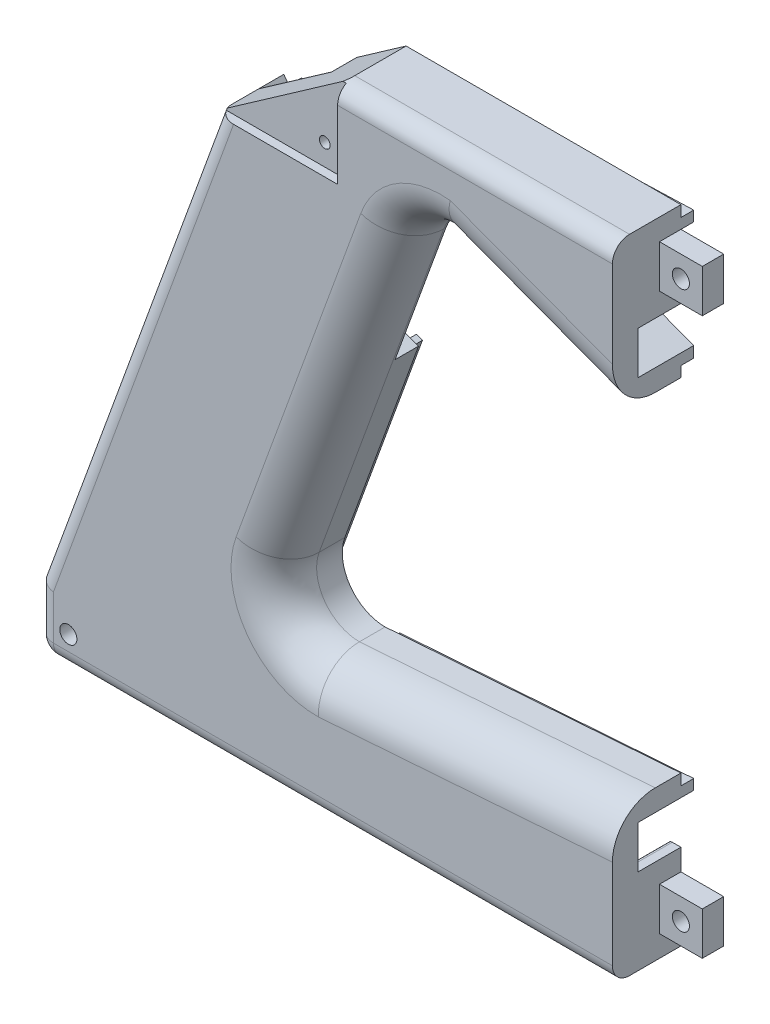
SolidWorks part; units mm, degrees
ref_plane "Ebene vorne" through (0, 0, 0) normal (0, 0, 1) x (1, 0, 0)
ref_plane "Ebene oben" through (0, 0, 0) normal (0, 1, 0) x (1, 0, 0)
ref_plane "Ebene rechts" through (0, 0, 0) normal (1, 0, 0) x (0, 0, -1)
sketch "Skizze1" plane through (0, 0, 0) normal (0, 0, 1) x (1, 0, 0)
  line L0 (-49.3963, -26.5806) -> (-78.5059, -106.5806)
  line L1 (0, -35) -> (-40, -20)
  line L2 (0, 0) -> (0, -35)
  line L3 (0, -115) -> (0, -150)
  line L4 (-69.1078, -120) -> (0, -115)
  line L5 (-134.6051, -135) -> (-134.6051, -150)
  line L6 (0, 0) -> (-64.1971, 0)
  line L7 (-64.1971, 0) -> (-92.76, -20)
  line L8 (-92.76, -20) -> (-134.6051, -135)
  line L9 (-134.6051, -150) -> (0, -150)
  arc A0 (-40, -20) -> (-49.3963, -26.5806) centre (-39.9991, -30) ccw
  arc A1 (-78.5059, -106.5806) -> (-69.1078, -120) centre (-69.1087, -110) ccw
  dimension "D6" = 110
  dimension "D5" = 70
  dimension "D3" = 10
  dimension "D4" = 10
  dimension "D1" = 35
  dimension "D2" = 40
  dimension "D7" = 80
  dimension "D8" = 69.1078
  dimension "D9" = 15
  dimension "D10" = 9.3972
  dimension "D11" = 9.3972
  dimension "D12" = 69.2894
  dimension "D13" = 35
  dimension "D14" = 15
  dimension "D15" = 20
  dimension "D17" = 43
  dimension "D18" = 35
extrude "Aufsatz-Linear austragen1" add sketch "Skizze1" along normal blind 16
sketch "Skizze2" plane through (0, 0, 0) normal (1, 0, 0) x (0, 0, -1)
  line L0 (0, -35) -> (0, 0) construction
  line L1 (0, -5) -> (-5, -5)
  line L2 (0, -5) -> (0, -15)
  line L3 (0, -15) -> (-5, -15)
  line L4 (-5, -5) -> (-5, -15)
  line L5 (-16, 0) -> (0, 0) construction
  dimension "D1" = 5
  dimension "D2" = 10
  dimension "D3" = 5
extrude "Aufsatz-Linear austragen2" add sketch "Skizze2" along normal blind 10
sketch "Skizze3" plane through (0, 0, 5) normal (0, 0, 1) x (1, 0, 0)
  line L0 (10, -15) -> (0, -15) construction
  line L1 (10, -5) -> (10, -15) construction
  circle A0 centre (5, -10) radius 2
  dimension "D2" = 4
  dimension "D1" = 5
  dimension "D3" = 5
extrude "Schnitt-Linear austragen1" cut sketch "Skizze3" against normal through all
sketch "Skizze4" plane through (0, 0, 0) normal (1, 0, 0) x (0, 0, -1)
  line L0 (0, -150) -> (0, -115) construction
  line L1 (0, -135) -> (-5, -135)
  line L2 (0, -135) -> (0, -145)
  line L3 (0, -145) -> (-5, -145)
  line L4 (-5, -135) -> (-5, -145)
  line L5 (-16, -150) -> (0, -150) construction
  dimension "D1" = 5
  dimension "D2" = 10
  dimension "D3" = 5
extrude "Aufsatz-Linear austragen3" add sketch "Skizze4" along normal blind 10
sketch "Skizze5" plane through (0, 0, 5) normal (0, 0, 1) x (1, 0, 0)
  line L0 (10, -135) -> (10, -145) construction
  line L1 (10, -135) -> (0, -135) construction
  circle A0 centre (5, -140) radius 2
  dimension "D1" = 4
  dimension "D2" = 5
  dimension "D3" = 5
extrude "Schnitt-Linear austragen2" cut sketch "Skizze5" against normal through all
sketch "Skizze10" plane through (0, 0, 16) normal (0, 0, 1) x (1, 0, 0)
  line L0 (-92.76, -20) -> (-64.1971, -20)
  line L1 (-64.1971, -20) -> (-64.1971, 0)
  line L2 (-64.1971, 0) -> (-92.76, -20) construction
  line L3 (-64.1971, 0) -> (-92.76, -20)
  dimension "D1" = 20
extrude "Schnitt-Linear austragen3" cut sketch "Skizze10" against normal blind 2
sketch "Skizze11" plane through (0, 0, 14) normal (0, 0, 1) x (1, 0, 0)
  line L0 (-64.1971, -20) -> (-64.1971, 0) construction
  line L1 (-92.76, -20) -> (-64.1971, -20) construction
  circle A0 centre (-69.1971, -15) radius 1.25
  dimension "D1" = 2.5
  dimension "D2" = 5
  dimension "D3" = 5
extrude "Schnitt-Linear austragen4" cut sketch "Skizze11" against normal through all
sketch "Skizze13" plane through (0, 0, 16) normal (0, 0, 1) x (1, 0, 0)
  line L0 (-134.6051, -150) -> (0, -150) construction
  line L1 (-134.6051, -135) -> (-134.6051, -150) construction
  circle A0 centre (-127.1051, -142.5) radius 2
  dimension "D3" = 4
  dimension "D1" = 7.5
  dimension "D2" = 7.5
extrude "Schnitt-Linear austragen5" cut sketch "Skizze13" against normal through all
sketch "Skizze14" plane through (0, 0, 0) normal (0, 0, -1) x (-1, 0, 0)
  line L0 (134.6051, -135) -> (134.6051, -150)
  line L1 (134.6051, -135) -> (134.6051, -150) construction
  line L2 (134.6051, -150) -> (89.6051, -150)
  line L3 (134.6051, -150) -> (0, -150) construction
  line L4 (89.6051, -150) -> (89.6051, -145)
  line L5 (89.6051, -145) -> (59.6051, -145)
  line L6 (59.6051, -145) -> (59.6051, -140)
  line L7 (59.6051, -140) -> (119.6051, -140)
  line L8 (119.6051, -140) -> (119.6051, -135)
  line L9 (119.6051, -135) -> (134.6051, -135)
  dimension "D1" = 15
  dimension "D2" = 45
  dimension "D3" = 60
  dimension "D4" = 5
  dimension "D5" = 5
  dimension "D6" = 15
extrude "Schnitt-Linear austragen6" cut sketch "Skizze14" against normal blind 9
sketch "Skizze15" plane through (0, 0, 0) normal (0, 0, -1) x (-1, 0, 0)
  line L0 (108.9626, -73.3019) -> (131.4126, -135)
  line L1 (134.6051, -135) -> (119.6051, -135) construction
  line L2 (131.4126, -135) -> (119.6051, -135)
  line L3 (119.6051, -135) -> (119.6051, -140)
  line L4 (119.6051, -140) -> (101.6596, -140)
  line L5 (119.6051, -140) -> (59.6051, -140) construction
  line L6 (108.9626, -73.3019) -> (99.5638, -47.4719)
  line L7 (99.5638, -47.4719) -> (64.794, -60.1236)
  line L8 (64.794, -60.1236) -> (93.8587, -140)
  line L9 (93.8587, -140) -> (101.6596, -140)
  line L10 (92.76, -20) -> (134.6051, -135) construction
  line L11 (78.5059, -106.5806) -> (49.3963, -26.5806) construction
  dimension "D1" = 3
  dimension "D2" = 3
  dimension "D3" = 85
extrude "Schnitt-Linear austragen7" cut sketch "Skizze15" against normal blind 9
sketch "Skizze24" plane through (0, 0, 0) normal (0, 0, -1) x (-1, 0, 0)
  line L0 (61.291, -59.2699) -> (49.3963, -26.5806)
  line L1 (78.5059, -106.5806) -> (49.3963, -26.5806) construction
  line L2 (49.3963, -26.5806) -> (40, -20)
  line L3 (40, -20) -> (40, -15.9566)
  line L4 (61.291, -59.2699) -> (64.1102, -58.2441)
  line L5 (64.1102, -58.2441) -> (48.723, -15.9566)
  line L6 (48.723, -15.9566) -> (40, -15.9566)
  line L7 (99.5638, -47.4719) -> (64.794, -60.1236) construction
  dimension "D1" = 3
  dimension "D2" = 45
  dimension "D3" = 2
extrude "Schnitt-Linear austragen17" cut sketch "Skizze24" against normal blind 5.5
sketch "Skizze25" plane through (0, 0, 0) normal (0, 0, -1) x (-1, 0, 0)
  line L0 (64.1102, -58.2441) -> (68.8088, -56.5344)
  line L1 (68.8088, -56.5344) -> (59.2345, -30.2222)
  line L2 (59.2345, -30.2222) -> (54.5359, -31.9319)
  line L3 (64.1102, -58.2441) -> (48.723, -15.9566) construction
  line L4 (54.5359, -31.9319) -> (64.1102, -58.2441)
  dimension "D1" = 5
  dimension "D2" = 28
extrude "Schnitt-Linear austragen18" cut sketch "Skizze25" against normal blind 7.5
sketch "Skizze27" plane through (0, 0, 0) normal (0, 0, -1) x (-1, 0, 0)
  line L0 (59.2345, -30.2222) -> (54.5359, -31.9319)
  line L1 (54.5359, -31.9319) -> (48.723, -15.9566)
  line L2 (48.723, -15.9566) -> (40, -15.9566)
  line L3 (40, -15.9566) -> (40, -20)
  line L4 (40, -20) -> (34.4371, -22.0861)
  line L5 (40, -20) -> (0, -35) construction
  line L6 (34.4371, -22.0861) -> (31.6281, -14.5954)
  line L7 (31.6281, -14.5954) -> (31.6281, -6.5954)
  line L8 (31.6281, -6.5954) -> (59.2345, -7.2222)
  line L9 (59.2345, -7.2222) -> (59.2345, -30.2222)
  dimension "D1" = 8
  dimension "D2" = 8
  dimension "D3" = 27.6064
  dimension "D4" = 23
extrude "Schnitt-Linear austragen19" cut sketch "Skizze27" against normal blind 5.5
sketch "Skizze28" plane through (0, 0, 5.5) normal (0, 0, -1) x (-1, 0, 0)
  line L0 (54.5359, -31.9319) -> (64.1102, -58.2441) construction
  line L2 (59.2345, -30.2222) -> (54.5359, -31.9319) construction
  circle A0 centre (45.5619, -16.0427) radius 1.5
  dimension "D2" = 3
  dimension "D1" = 3
  dimension "D3" = 18
sketch "Skizze29" plane through (0, 0, 0) normal (0, 0, -1) x (-1, 0, 0)
  line L0 (68.8088, -56.5344) -> (83.8443, -51.0634)
  line L1 (83.8443, -51.0634) -> (73.2443, -21.932)
  line L2 (73.2443, -21.932) -> (58.2087, -27.403)
  line L3 (58.2087, -27.403) -> (68.8088, -56.5344)
  dimension "D1" = 16
  dimension "D2" = 31
extrude "Schnitt-Linear austragen20" cut sketch "Skizze29" against normal blind 5
sketch "Skizze30" plane through (0, 0, 5) normal (0, 0, -1) x (-1, 0, 0)
  line L0 (68.8088, -56.5344) -> (83.8443, -51.0634) construction
  line L1 (83.8443, -51.0634) -> (73.2443, -21.932) construction
  circle A0 centre (80.7257, -49.8039) radius 1.25
  dimension "D1" = 2.5
  dimension "D2" = 2.25
  dimension "D3" = 2.5
extrude "Aufsatz-Linear austragen9" add sketch "Skizze30" along normal blind 5
sketch "Skizze31" plane through (0, 0, 5) normal (0, 0, -1) x (-1, 0, 0)
  line L0 (59.2345, -30.2222) -> (68.8088, -56.5344) construction
  line L1 (73.2443, -21.932) -> (59.2345, -27.0298) construction
  circle A0 centre (61.0925, -28.748) radius 1.25
  dimension "D1" = 2.5
  dimension "D2" = 2.25
  dimension "D3" = 2.25
extrude "Aufsatz-Linear austragen10" add sketch "Skizze31" along normal blind 5
sketch "Skizze16" plane through (0, 0, 0) normal (0, 0, -1) x (-1, 0, 0)
  line L0 (0, -20) -> (0, -30)
  line L1 (0, -35) -> (0, -15) construction
  line L2 (3, -5) -> (31.6281, -6.5954)
  line L3 (0, -30) -> (32.7933, -17.7025)
  line L4 (31.6281, -14.5954) -> (34.4371, -22.0861) construction
  line L5 (32.7933, -17.7025) -> (31.6281, -14.5954)
  line L6 (0, -20) -> (3, -20)
  line L7 (3, -20) -> (3, -5)
  line L8 (31.6281, -14.5954) -> (31.6281, -6.5954)
  dimension "D1" = 5
  dimension "D2" = 10
  dimension "D3" = 28.6725
  dimension "D6" = 3
extrude "Schnitt-Linear austragen9" cut sketch "Skizze16" against normal blind 7
sketch "Skizze32" plane through (0, 0, 0) normal (0, 0, -1) x (-1, 0, 0)
  line L0 (59.2345, -27.0298) -> (70.4251, -22.9578)
  line L1 (73.2443, -21.932) -> (59.2345, -27.0298) construction
  line L2 (70.4251, -22.9578) -> (69.3993, -20.1387)
  line L3 (69.3993, -20.1387) -> (75.0377, -18.087)
  line L4 (75.0377, -18.087) -> (76.4054, -21.8459)
  line L5 (76.4054, -21.8459) -> (73.5862, -22.8717)
  line L6 (83.8443, -51.0634) -> (73.2443, -21.932) construction
  line L7 (73.5862, -22.8717) -> (80.425, -41.6662)
  line L9 (87.3474, -51.9171) -> (99.5638, -47.4719)
  line L10 (99.5638, -47.4719) -> (90.2643, -21.9148)
  line L11 (90.2643, -21.9148) -> (69.2811, -7.2222)
  line L12 (69.2811, -7.2222) -> (59.2345, -7.2222)
  line L13 (64.1971, 0) -> (92.76, -20) construction
  line L14 (59.2345, -7.2222) -> (59.2345, -27.0298)
  line L15 (80.425, -41.6662) -> (83.2441, -40.6404)
  line L16 (83.2441, -40.6404) -> (87.3474, -51.9171)
  dimension "D1" = 3
  dimension "D2" = 3
  dimension "D3" = 1
  dimension "D4" = 3
  dimension "D5" = 3
  dimension "D6" = 10
  dimension "D7" = 13
  dimension "D8" = 12
  dimension "D9" = 27.1964
  dimension "D10" = 3
extrude "Schnitt-Linear austragen21" cut sketch "Skizze32" against normal blind 10
sketch "Skizze17" plane through (0, 0, 0) normal (0, 0, -1) x (-1, 0, 0)
  line L0 (0, -130) -> (0, -120)
  line L1 (0, -135) -> (0, -115) construction
  line L2 (0, -120) -> (68.6763, -124.9688)
  line L3 (68.6763, -124.9688) -> (86.0844, -118.6345)
  line L4 (64.794, -60.1236) -> (93.8587, -140) construction
  line L5 (86.0844, -118.6345) -> (93.8587, -140)
  line L6 (93.8587, -140) -> (59.6051, -140)
  line L7 (59.6051, -140) -> (59.6051, -145)
  line L8 (59.6051, -145) -> (3, -145)
  line L9 (3, -145) -> (3, -130)
  line L10 (3, -130) -> (0, -130)
  line L11 (0, -115) -> (69.1078, -120) construction
  dimension "D1" = 5
  dimension "D2" = 4.987
  dimension "D3" = 18.5247
  dimension "D4" = 3
extrude "Schnitt-Linear austragen10" cut sketch "Skizze17" against normal blind 7
sketch "Skizze18" plane through (0, 0, 7) normal (0, 0, -1) x (-1, 0, 0)
  line L0 (0, -130) -> (10, -130)
  line L1 (10, -130) -> (10, -120.7235)
  line L2 (68.6763, -124.9688) -> (0, -120) construction
  line L3 (10, -120.7235) -> (0, -120)
  line L4 (0, -120) -> (0, -130)
  dimension "D1" = 10
extrude "Schnitt-Linear austragen11" cut sketch "Skizze18" against normal blind 3
sketch "Skizze19" plane through (0, 0, 7) normal (0, 0, -1) x (-1, 0, 0)
  line L0 (0, -20) -> (0, -30)
  line L1 (0, -20) -> (10, -20)
  line L2 (10, -20) -> (10, -26.25)
  line L3 (10, -26.25) -> (0, -30)
  line L4 (0, -30) -> (32.7933, -17.7025) construction
  dimension "D1" = 10
extrude "Schnitt-Linear austragen12" cut sketch "Skizze19" against normal blind 3
sketch "Skizze20" plane through (-21.1202, 30.1628, 0) normal (-0.5736, 0.8192, 0) x (0.8192, 0.5736, 0)
  line L0 (-52.5872, 0) -> (-87.4561, 0) construction
  line L1 (-69.5872, 0) -> (-67.5872, 0)
  line L2 (-69.5872, 0) -> (-69.5872, -5)
  line L3 (-69.5872, -5) -> (-67.5872, -5)
  line L4 (-67.5872, 0) -> (-67.5872, -5)
  dimension "D1" = 5
  dimension "D2" = 2
  dimension "D3" = 15
extrude "Schnitt-Linear austragen13" cut sketch "Skizze20" against normal blind 10
sketch "Skizze23" plane through (-21.1202, 30.1628, 0) normal (-0.5736, 0.8192, 0) x (0.8192, 0.5736, 0)
  line L0 (-87.4561, -14) -> (-87.4561, 0) construction
  line L1 (-69.5872, 0) -> (-87.4561, 0)
  line L2 (-69.5872, 0) -> (-69.5872, -5)
  line L3 (-69.5872, -5) -> (-87.4561, -5)
  line L4 (-87.4561, 0) -> (-87.4561, -5)
extrude "Schnitt-Linear austragen16" cut sketch "Skizze23" against normal blind 2
fillet "Verrundung4" radius 1 3 edges at (-84.6222, -14.3018, 5) (-76.4843, -8.6036, 2.5) (-76.9755, -11.3891, 2.5)
fillet "Verrundung5" radius 1 6 edges at (-3, -130, 3.5) (-6.5, -130, 7) (-10, -125.3618, 7) (-6.5, -20, 7) (-3, -20, 3.5) (-10, -23.125, 7)
fillet "Verrundung1" radius 10 5 edges at (-77.2997, -115.7365, 16) (-45.7356, -21.809, 16) (-63.9511, -66.5806, 16) (-20, -27.5, 16) (-34.5539, -117.5, 16)
fillet "Verrundung2" radius 4 4 edges at (-67.3025, -150, 16) (-134.6051, -142.5, 16) (-113.6825, -77.5, 16) (-32.0985, 0, 16)
fillet "Verrundung3" radius 4 2 edges at (-133.4335, -148.8284, 14.8284) (-134.6051, -150, 10.5)
sketch "Sketch3" plane through (0, 0, 0) normal (0, 0, -1) x (-1, 0, 0)
  line L1 (0, -147.4) -> (89.6051, -147.4)
  line L2 (0, -147.4) -> (0, -145)
  line L3 (0, -145) -> (89.6051, -145)
  line L4 (89.6051, -147.4) -> (89.6051, -145)
  line L5 (0, -120) -> (68.6763, -124.9688)
  line L6 (68.6763, -124.9688) -> (68.6763, -122.4844)
  line L7 (68.6763, -122.4844) -> (0, -117.6)
  line L9 (0, -117.6) -> (0, -120)
  line L10 (131.4126, -135) -> (90.2643, -21.9148)
  line L11 (90.2643, -21.9148) -> (91.6129, -21.6383)
  line L12 (91.6129, -21.6383) -> (132.8618, -135)
  line L13 (134.6051, -135) -> (131.4126, -135) construction
  line L14 (132.8618, -135) -> (131.4126, -135)
  line L15 (0, -5) -> (69.2811, -7.2222)
  line L16 (69.2811, -7.2222) -> (64.1971, -4.6591)
  line L17 (64.1971, -4.6591) -> (0, -2.6)
  line L19 (0, -2.6) -> (0, -5)
  line L20 (86.0844, -118.6345) -> (64.794, -60.1236)
  line L21 (64.794, -60.1236) -> (63.3845, -60.6365)
  line L22 (63.3845, -60.6365) -> (84.6748, -119.1474)
  line L23 (86.0844, -118.6345) -> (68.6763, -124.9688) construction
  line L24 (84.6748, -119.1474) -> (86.0844, -118.6345)
  line L25 (0, -30) -> (32.7933, -17.7025)
  line L26 (32.7933, -17.7025) -> (33.636, -19.9497)
  line L27 (32.7933, -17.7025) -> (34.4371, -22.0861) construction
  line L28 (33.636, -19.9497) -> (0, -32.5632)
  line L29 (0, -32.5632) -> (0, -30)
  dimension "D1" = 2.4
  dimension "D2" = 2.4
  dimension "D3" = 0
  dimension "D4" = 2.4
  dimension "D5" = 1.5
  dimension "D6" = 2.4
extrude "Boss-Extrude2" add sketch "Sketch3" along normal blind 3
extrude "Schnitt-Linear austragen22" cut sketch "Skizze28" against normal blind 4 contours A0
